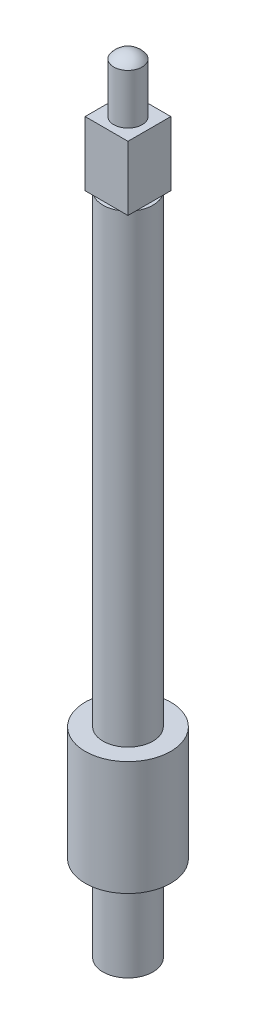
SolidWorks part; units mm, degrees
ref_plane "Front Plane" through (0, 0, 0) normal (0, 0, 1) x (1, 0, 0)
ref_plane "Top Plane" through (0, 0, 0) normal (0, 1, 0) x (1, 0, 0)
ref_plane "Right Plane" through (0, 0, 0) normal (1, 0, 0) x (0, 0, -1)
sketch "Sketch1" plane through (0, 0, 0) normal (0, 1, 0) x (1, 0, 0)
  circle A0 centre (0, 0) radius 5.985
  dimension "D1" = 11.97
extrude "Boss-Extrude1" add sketch "Sketch1" along normal blind 16
cosmetic thread "Cosmetic Thread3" parameters "D2"=10.072
sketch "Sketch2" plane through (0, 16, 0) normal (0, 1, 0) x (1, 0, 0)
  circle A0 centre (0, 0) radius 3.5
  dimension "D1" = 7
extrude "Boss-Extrude2" add sketch "Sketch2" along normal blind 65
sketch "Sketch3" plane through (0, 81, 0) normal (0, 1, 0) x (1, 0, 0)
  line L1 (-3, 3) -> (3, 3)
  line L2 (-3, 3) -> (-3, -3)
  line L3 (-3, -3) -> (3, -3)
  line L4 (3, 3) -> (3, -3)
  line L5 (-3, 3) -> (3, -3) construction
  line L6 (-3, -3) -> (3, 3) construction
  point P0 (0, 0)
  dimension "D1" = 6
  dimension "D2" = 6
extrude "Boss-Extrude3" add sketch "Sketch3" along normal blind 9
sketch "Sketch4" plane through (0, 90, 0) normal (0, 1, 0) x (1, 0, 0)
  circle A0 centre (0, 0) radius 1.99
  dimension "D1" = 3.98
extrude "Boss-Extrude4" add sketch "Sketch4" along normal blind 7 contours A0
cosmetic thread "Cosmetic Thread1" parameters "D1"=6, "D2"=3.22
sketch "Sketch5" plane through (0, 0, 0) normal (0, -1, 0) x (1, 0, 0)
  circle A0 centre (0, 0) radius 3.5
  dimension "D1" = 7
extrude "Boss-Extrude5" add sketch "Sketch5" along normal blind 12
hole_wizard "Tap Drill for M4 Tap1" positions "Sketch14" profile "Sketch15" hole size "M4" standard "ISO"
sketch "Sketch14" plane through (0, -12, 0) normal (0, -1, 0) x (-1, 0, 0)
  point P0 (0, 0)
cosmetic thread "Cosmetic Thread4" parameters "D1"=7.5, "D2"=4
sketch "Sketch15" plane through (0, -12, 0) normal (1, 0, 0) x (0, 0, -1)
  line L0 (0, 0) -> (0, 9.9914)
  line L1 (0, 9.9914) -> (1.65, 9)
  line L2 (1.65, 9) -> (1.65, 0)
  line L5 (1.65, 0) -> (0, 0)
  line L10 (0, 9.9914) -> (-1.65, 9) construction
  line L11 (0, -6.35) -> (0, 107.95) construction
  dimension "Hole Dia." = 3.3
  dimension "Hole Depth" = 9
  dimension "Drill Angle" = 118
dome "Dome1" faces to dome 1 distance 1 reverse direction no elliptical dome no face at (0, 97, 1.99) parameters "D1"=1
